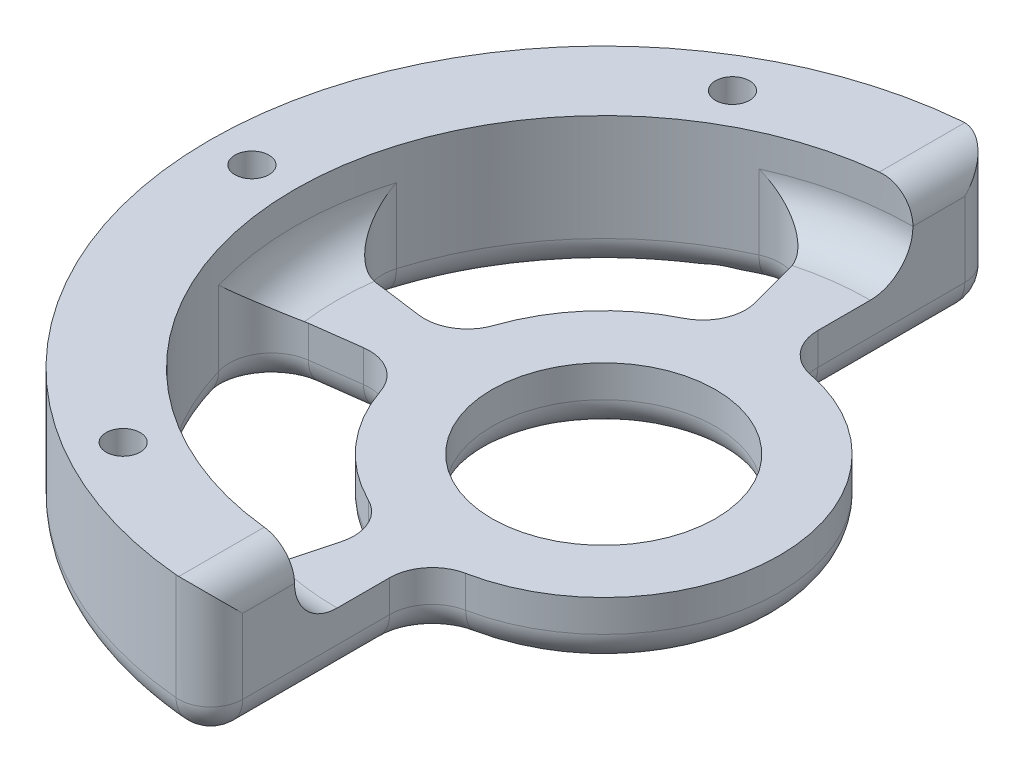
SolidWorks part; units mm, degrees
ref_plane "Front Plane" through (0, 0, 0) normal (0, 0, 1) x (1, 0, 0)
ref_plane "Top Plane" through (0, 0, 0) normal (0, 1, 0) x (1, 0, 0)
ref_plane "Right Plane" through (0, 0, 0) normal (1, 0, 0) x (0, 0, -1)
sketch "Sketch1" plane through (0, 0, 0) normal (0, 1, 0) x (1, 0, 0)
  line L0 (-13.0077, -7.51) -> (43288.2625, 24992.49) construction
  line L1 (0, -15.02) -> (0, 49984.98) construction
  line L2 (-32.0776, -18.52) -> (-25.1494, -14.52)
  line L3 (0, -37.04) -> (0, -29.04)
  line L4 (0, 0) -> (-25000, -43301.2702) construction
  line L5 (-32.0776, -18.52) -> (-25.1494, -14.52)
  line L6 (-32.0776, 18.52) -> (-25.1494, 14.52)
  line L7 (-32.0776, 18.52) -> (-25.1494, 14.52)
  line L8 (0, 37.04) -> (0, 29.04)
  circle A0 centre (0, 0) radius 37.04 construction
  circle A1 centre (0, 0) radius 33.04 construction
  circle A2 centre (0, 0) radius 29.04 construction
  arc A3 (-25.1494, -14.52) -> (0, -29.04) centre (0, 0) ccw
  arc A4 (0, -37.04) -> (-32.0776, -18.52) centre (0, 0) cw
  circle A5 centre (-16.52, -28.6135) radius 1.6
  arc A6 (-25.1494, 14.52) -> (-25.1494, -14.52) centre (0, 0) ccw
  arc A7 (-32.0776, -18.52) -> (-32.0776, 18.52) centre (0, 0) cw
  circle A8 centre (-33.04, 0) radius 1.6
  arc A9 (0, 29.04) -> (-25.1494, 14.52) centre (0, 0) ccw
  arc A10 (-32.0776, 18.52) -> (0, 37.04) centre (0, 0) cw
  circle A11 centre (-16.52, 28.6135) radius 1.6
  point P13 (-16.52, -28.6135)
  point P18 (-25.1724, 16.3937)
  point P20 (-25.6325, -15.6645)
  point P33 (0, 0)
  dimension "D1" = 58.08
  dimension "D2" = 66.08
  dimension "D3" = 74.08
  dimension "D5" = 3.2
  dimension "D4" = 60
  dimension "D6" = 30
  dimension "D7" = 3
extrude "Boss-Extrude1" add sketch "Sketch1" along normal blind 7 contours A4 L3 A3 L2 A5 | A7 L2 A6 L6 A8 | A10 L6 A9 L8 A11 region at (-36.651, 0, 0) region at (-28.4175, 0, 16.8594) region at (-18.324, 0, -31.7382)
sketch "Sketch2" plane through (0, 0, 0) normal (0, -1, 0) x (1, 0, 0)
  line L0 (0, -29.04) -> (0, -16.5)
  line L1 (-4.2705, -15.9378) -> (-7.5161, -28.0505)
  line L2 (-28.7916, -3.7905) -> (-16.3588, -2.1537)
  line L3 (-16.3588, 2.1537) -> (-28.7916, 3.7905)
  line L4 (-7.5161, 28.0505) -> (-4.2705, 15.9378)
  line L5 (0, 16.5) -> (0, 29.04)
  line L6 (0, 37.04) -> (0, 29.04) construction
  line L7 (0, 0) -> (-25000, -43301.2702) construction
  line L8 (0, 0) -> (-30438.0715, -39667.667) construction
  line L9 (0, 0) -> (-19134.1716, -46193.9766) construction
  line L10 (-11.1131, -26.8295) -> (-14.1746, -34.2205)
  line L11 (-22.5485, -29.3858) -> (-17.6784, -23.039)
  line L12 (-36.7231, 4.8347) -> (-28.7916, 3.7905)
  line L13 (-28.7916, -3.7905) -> (-36.7231, -4.8347)
  line L14 (-14.1746, 34.2205) -> (-11.1131, 26.8295)
  line L15 (-17.6784, 23.039) -> (-22.5485, 29.3858)
  line L16 (0, 0) -> (-50000, 0) construction
  circle A0 centre (0, 0) radius 10.5
  circle A1 centre (0, 0) radius 16.5
  arc A2 (0, 29.04) -> (0, -29.04) centre (0, 0) ccw construction
  arc A3 (-7.5161, -28.0505) -> (0, -29.04) centre (0, 0) ccw
  arc A4 (-28.7916, 3.7905) -> (-28.7916, -3.7905) centre (0, 0) ccw
  arc A5 (0, 29.04) -> (-7.5161, 28.0505) centre (0, 0) ccw
  arc A6 (-22.5485, -29.3858) -> (-14.1746, -34.2205) centre (0, 0) ccw
  arc A7 (-17.6784, -23.039) -> (-11.1131, -26.8295) centre (0, 0) ccw
  arc A8 (0, 37.04) -> (0, -37.04) centre (0, 0) ccw construction
  arc A9 (-28.7916, 3.7905) -> (-28.7916, -3.7905) centre (0, 0) ccw
  arc A10 (-36.7231, 4.8347) -> (-36.7231, -4.8347) centre (0, 0) ccw
  arc A11 (-11.1131, 26.8295) -> (-17.6784, 23.039) centre (0, 0) ccw
  arc A12 (-14.1746, 34.2205) -> (-22.5485, 29.3858) centre (0, 0) ccw
  circle A13 centre (-16.52, -28.6135) radius 3.25
  circle A14 centre (-33.04, 0) radius 3.25
  circle A15 centre (-16.52, 28.6135) radius 3.25
  point P22 (0, 0)
  point P47 (0, 0)
  point P50 (-37.04, 0)
  circle M6 centre (-16.52, 28.6135) radius 1.6
  arc M7 (0, 37.04) -> (0, -37.04) centre (0, 0) ccw
  line M8 (0, -37.04) -> (0, -29.04)
  arc M9 (0, -29.04) -> (0, 29.04) centre (0, 0) cw
  line M10 (0, 29.04) -> (0, 37.04)
  circle M11 centre (-33.04, 0) radius 1.6
  circle M12 centre (-16.52, -28.6135) radius 1.6
  dimension "D1" = 21
  dimension "D2" = 6
  dimension "D8" = 6.5
  dimension "D3" = 15
  dimension "D4" = 3
  dimension "D5" = 7.5
  dimension "D6" = 7.5
  dimension "D7" = 3
extrude "Boss-Extrude2" add sketch "Sketch2" along normal blind 6 contours A1 L5 L4 M9 | A1 L3 L2 M9 | A1 A0 | A1 L1 L0 M9 | M10 M7 M8 M9 M12 M11 M6 | L10 M9 M7 M8 | L11 L10 M7 M9 M12 | L13 L11 M9 M7 | L15 L12 M9 M7 | L14 M7 M9 M10 | L15 L14 M9 M7 M6 region at (-3.0385, 0, -23.0797) region at (-6.4357, 0, -32.3546) region at (-2.0928, 0, -15.8961) region at (-12.7916, 0, -30.4638) region at (-23.2789, 0, 0) region at (-3.0385, 0, 23.0797) region at (-28.0199, 0, -16.1773) region at (-32.7739, 0, -4.1866) region at (-6.4357, 0, 32.3546) region at (-28.0199, 0, 16.1773) region at (-19.9866, 0, 26.3098)
fillet "Fillet1" radius 4 13 edges at (-7.5161, -3, 28.0505) (-3.7905, 0, 28.7916) (-28.7916, -3, 3.7905) (-28.7916, -3, -3.7905) (-29.04, 0, 0) (-7.5161, -3, -28.0505) (-3.7905, 0, -28.7916) (0, -3, -16.5) (0, -3, 16.5) (-4.2705, -3, 15.9378) (-16.3588, -3, 2.1537) (-16.3588, -3, -2.1537) (-4.2705, -3, -15.9378)
sketch "Sketch4" plane through (0, -6, 0) normal (0, -1, 0) x (1, 0, 0)
  line L0 (-5.4376, 30.8379) -> (8676.9713, -49209.5497) construction
  line L1 (0, 0) -> (0, 50000) construction
  line L2 (-5.7373, -969.4347) -> (-5.7373, 49030.5653) construction
  circle A0 centre (-5.7373, 32.538) radius 2.25
  circle A1 centre (0, 0) radius 33.04 construction
  circle A2 centre (-29.5256, 14.8283) radius 2.25
  circle A3 centre (-29.5256, -14.8283) radius 2.25
  circle A4 centre (-5.7373, -32.538) radius 2.25
  point P11 (0, 0)
  point P12 (-5.7373, -30.5653)
  point P20 (0, 0)
  point P22 (-24.8424, -13.4894)
  point P23 (0, 0)
  dimension "D1" = 66.08
  dimension "D2" = 4.5
  dimension "D3" = 10
  dimension "D4" = 4
extrude "Cut-Extrude2" cut sketch "Sketch4" against normal blind 10
fillet "Fillet2" radius 3 27 edges at (-37.04, -6, 0) (0, 7, -33.04) (0, 7, 33.04) (0, -6, -28.573) (0.9079, -6, -17.5684) (16.5, -6, 0) (0.9079, -6, 17.5684) (-22.2205, -6, 2.9254) (-17.2996, -6, 3.1933) (-12.4054, -6, 10.8792) (-5.424, -6, 16.7348) (-5.8007, -6, 21.6485) (-8.5453, -6, 26.4541) (-21.8334, -6, 19.1474) (-8.5453, -6, -26.4541) (-5.8007, -6, -21.6485) (-5.424, -6, -16.7348) (-12.4054, -6, -10.8792) (-17.2996, -6, -3.1933) (-22.2205, -6, -2.9254) (-27.3432, -6, -5.0193) (0, -6, 28.573) (-27.3432, -6, 5.0193) (-21.8334, -6, -19.1474) (0, 0.5, -37.04) (0, 0.5, 37.04) (0, -6, -10.5)
